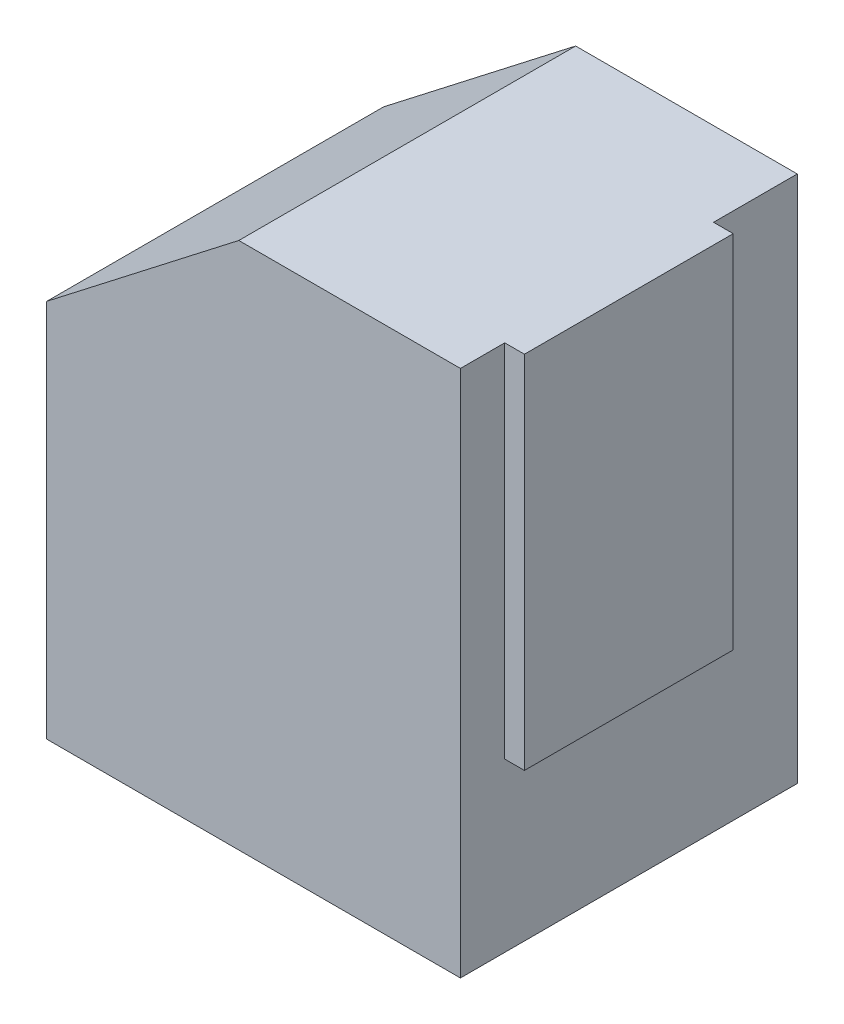
SolidWorks part; units mm, degrees
ref_plane "Front Plane" through (0, 0, 0) normal (0, 0, 1) x (1, 0, 0)
ref_plane "Top Plane" through (0, 0, 0) normal (0, 1, 0) x (1, 0, 0)
ref_plane "Right Plane" through (0, 0, 0) normal (1, 0, 0) x (0, 0, -1)
sketch "Sketch1" plane through (0, 0, 0) normal (0, 0, 1) x (1, 0, 0)
  line L0 (0, 38.5) -> (19.5, 53.6)
  line L1 (0, 0) -> (42, 0)
  line L2 (0, 0) -> (0, 38.5)
  line L3 (19.5, 53.6) -> (42, 53.6)
  line L4 (42, 0) -> (42, 53.6)
  dimension "D1" = 53.6
  dimension "D2" = 42
  dimension "D3" = 22.5
  dimension "D4" = 38.5
extrude "Boss-Extrude1" add sketch "Sketch1" along normal blind 34.2
sketch "Sketch2" plane through (0, 0, 0) normal (0, -1, 0) x (1, 0, 0)
  line L0 (42, 34.2) -> (42, 0) construction
  line L1 (0, 34.2) -> (42, 34.2) construction
  circle A0 centre (25, 23.2) radius 8
  dimension "D3" = 16
  dimension "D1" = 17
  dimension "D2" = 11
extrude "Cut-Extrude1" cut sketch "Sketch2" against normal blind 10
sketch "Sketch3" plane through (42, 0, 0) normal (1, 0, 0) x (0, 0, -1)
  line L0 (-34.2, 53.6) -> (0, 53.6) construction
  line L1 (-29.7, 53.6) -> (-8.5, 53.6)
  line L2 (-29.7, 53.6) -> (-29.7, 17)
  line L3 (-29.7, 17) -> (-8.5, 17)
  line L4 (-8.5, 53.6) -> (-8.5, 17)
  line L5 (-34.2, 0) -> (-34.2, 53.6) construction
  line L6 (0, 0) -> (0, 53.6) construction
  line L7 (-34.2, 0) -> (0, 0) construction
  dimension "D1" = 4.5
  dimension "D2" = 8.5
  dimension "D3" = 17
extrude "Boss-Extrude2" add sketch "Sketch3" along normal blind 2
sketch "Sketch4" plane through (0, 0, 0) normal (0, 0, -1) x (-1, 0, 0)
  line L0 (-42, 2) -> (-40, 0)
  line L1 (-42, 0) -> (-42, 53.6) construction
  line L2 (0, 0) -> (-42, 0) construction
  line L3 (-40, 0) -> (-42, 0)
  line L4 (-42, 0) -> (-42, 2)
  line L5 (0, 2) -> (-2, 0)
  line L6 (0, 38.5) -> (0, 0) construction
  line L7 (-2, 0) -> (0, 0)
  line L8 (0, 0) -> (0, 2)
  dimension "D1" = 45
  dimension "D2" = 2
  dimension "D3" = 2
extrude "Cut-Extrude3" [suppressed] cut sketch "Sketch4" against normal through all
fillet "Fillet1" [suppressed] radius 1
sketch "Sketch5" plane through (0, 0, 0) normal (0, 0, -1) x (-1, 0, 0)
  line L1 (-34.8, 3.8) -> (-3.8, 3.8) construction
  line L2 (-34.8, 3.8) -> (-34.8, 34.8) construction
  line L3 (-34.8, 34.8) -> (-3.8, 34.8) construction
  line L4 (-3.8, 3.8) -> (-3.8, 34.8) construction
  line L5 (0, 0) -> (-42, 0) construction
  line L6 (0, 38.5) -> (0, 0) construction
  circle A0 centre (-34.8, 3.8) radius 1.65
  circle A1 centre (-3.8, 3.8) radius 1.65
  circle A2 centre (-3.8, 34.8) radius 1.65
  dimension "D3" = 3.3
  dimension "D1" = 31
  dimension "D2" = 31
  dimension "D4" = 3.8
  dimension "D5" = 3.8
extrude "Cut-Extrude4" cut sketch "Sketch5" against normal blind 10
